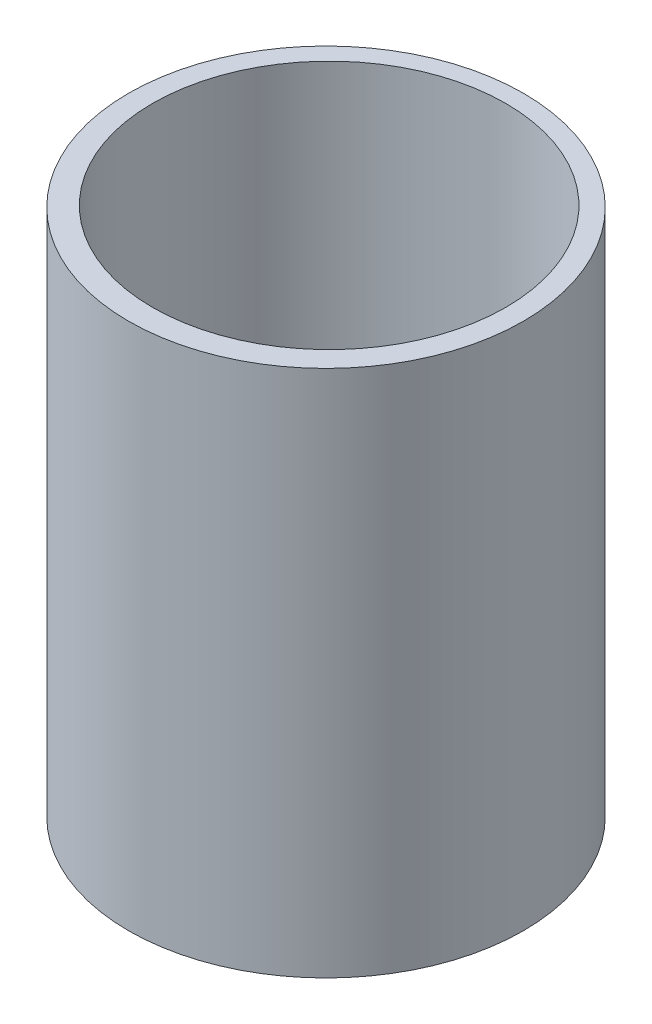
SolidWorks part; units mm, degrees
ref_plane "Front Plane" through (0, 0, 0) normal (0, 0, 1) x (1, 0, 0)
ref_plane "Top Plane" through (0, 0, 0) normal (0, 1, 0) x (1, 0, 0)
ref_plane "Right Plane" through (0, 0, 0) normal (1, 0, 0) x (0, 0, -1)
other "pvc"
sketch "PVC" plane through (0, 0, 0) normal (0, 1, 0) x (1, 0, 0)
  circle A0 centre (0, 0) radius 57
  circle A1 centre (0, 0.9079) radius 51
  dimension "OD" = 114
  dimension "ID" = 102
extrude "Boss-Extrude1" add sketch "PVC" along normal blind 152.4
